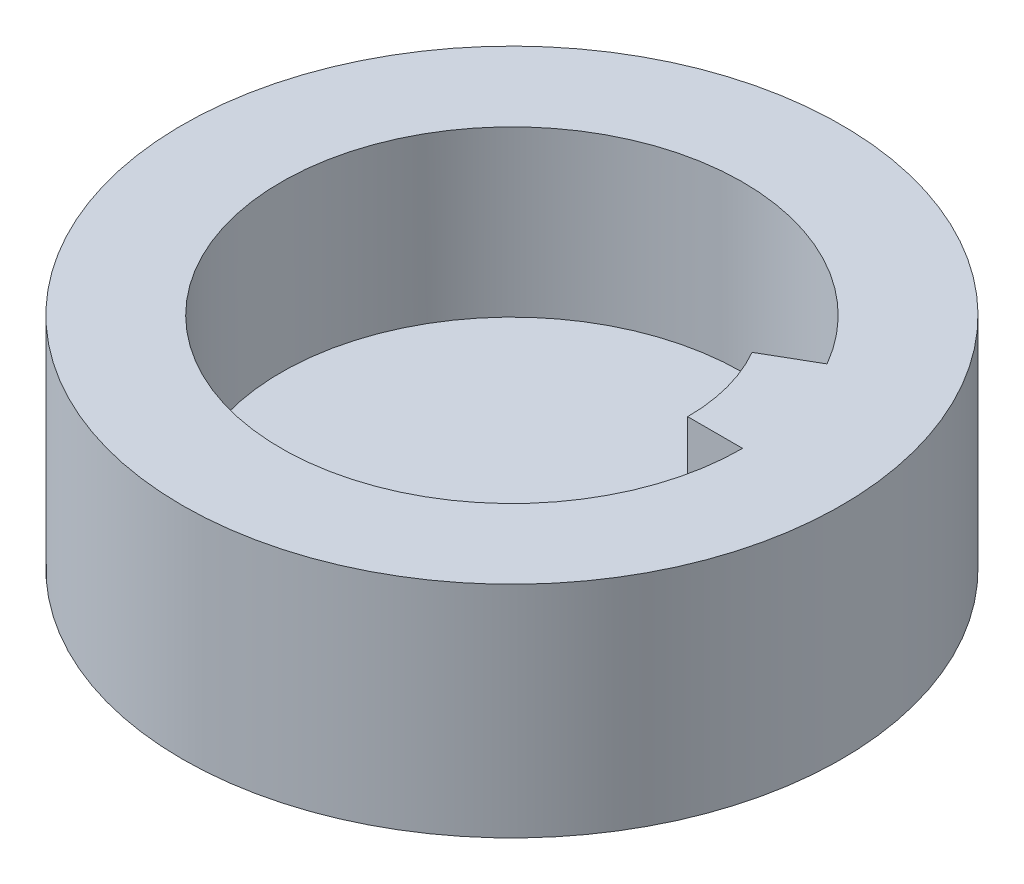
SolidWorks part; units mm, degrees
ref_plane "Alzado" through (0, 0, 0) normal (0, 0, 1) x (1, 0, 0)
ref_plane "Planta" through (0, 0, 0) normal (0, 1, 0) x (1, 0, 0)
ref_plane "Vista lateral" through (0, 0, 0) normal (1, 0, 0) x (0, 0, -1)
sketch "Sketch1" plane through (0, 0, 0) normal (0, 1, 0) x (1, 0, 0)
  line L0 (3.6373, 2.1) -> (2.7713, 1.6)
  line L1 (3.2, 0) -> (4.2, 0)
  circle A0 centre (0, 0) radius 6
  circle A1 centre (0, 0) radius 4.2
  arc A2 (4.2, 0) -> (3.6373, 2.1) centre (0, 0) ccw
  arc A3 (3.2, 0) -> (2.7713, 1.6) centre (0, 0) ccw
  dimension "D1" = 12
  dimension "D2" = 8.4
  dimension "D4" = 30
  dimension "D3" = 1
extrude "Boss-Extrude1" add sketch "Sketch1" along normal blind 4 contours A0 A1 region at (-5.8303, 0, 0)
extrude "Boss-Extrude2" add sketch "Sketch1<3>" along normal blind 1 from surface contours L1 A3 L0 A1 | A0 A1 | A3 L1 A1 L0 region at (3.5547, 0, -0.9525) region at (-0.1288, 0, 0.0345) region at (-5.8303, 0, 0) starting at face at (0, 0, 4.2)
sketch "Sketch1<3>" plane through (0, 0, 0) normal (0, 1, 0) x (1, 0, 0) same geometry as "Sketch1"
extrude "Boss-Extrude3" add sketch "Sketch1<4>" against normal blind 1.5 from surface contours A3 L1 A1 L0 region at (3.5547, 0, -0.9525) starting at face at (0, 4, 4.2)
sketch "Sketch1<4>" plane through (0, 0, 0) normal (0, 1, 0) x (1, 0, 0) same geometry as "Sketch1"
